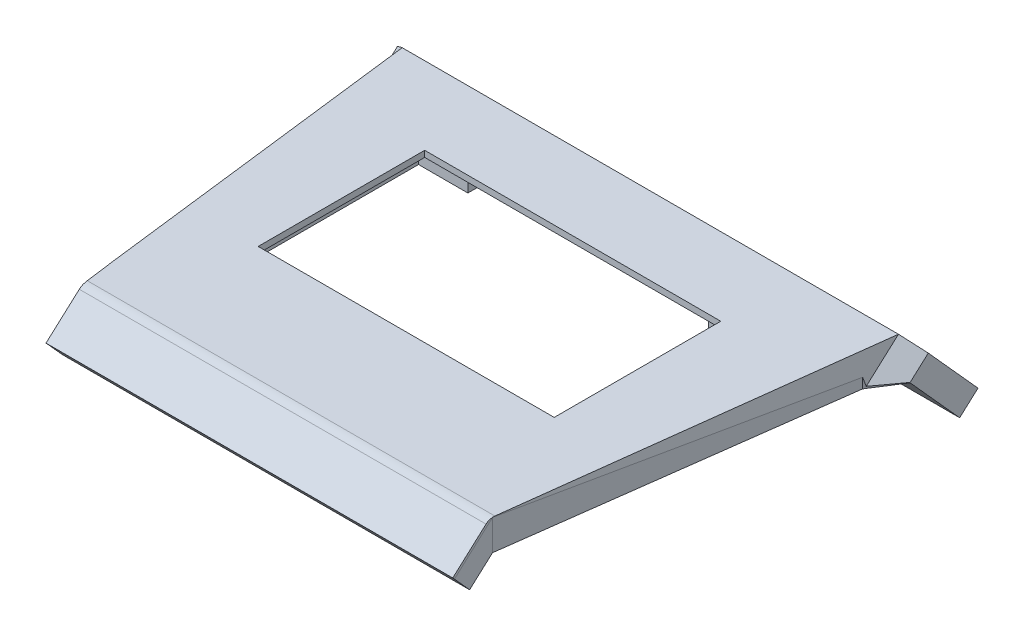
SolidWorks part; units mm, degrees
ref_plane "Front Plane" through (0, 0, 0) normal (0, 0, 1) x (1, 0, 0)
ref_plane "Top Plane" through (0, 0, 0) normal (0, 1, 0) x (1, 0, 0)
ref_plane "Right Plane" through (0, 0, 0) normal (1, 0, 0) x (0, 0, -1)
sketch "Sketch1" plane through (0, 0, 0) normal (0, 1, 0) x (1, 0, 0)
  line L0 (-16.5, -14.5) -> (16.5, -14.5)
  line L1 (16.5, -14.5) -> (20, 12)
  line L2 (-20, 12) -> (-21.25, 14.35)
  line L3 (-21.25, 14.35) -> (21.5, 14.35)
  line L4 (21.5, 14.35) -> (20, 12)
  line L5 (-20, 12) -> (-16.5, -14.5)
  line L7 (-13.75, 9.75) -> (13.75, 9.75)
  line L8 (-13.75, 9.75) -> (-13.75, -9.75)
  line L9 (-13.75, -9.75) -> (13.75, -9.75)
  line L10 (13.75, 9.75) -> (13.75, -9.75)
  dimension "D1" = 27.5
  dimension "D2" = 19.5
  dimension "D3" = 4.75
  dimension "D4" = 9.75
  dimension "D5" = 13.75
  dimension "D6" = 2.75
  dimension "D7" = 2.75
  dimension "D8" = 26.5
  dimension "D9" = 3.5
  dimension "D10" = 3.5
  dimension "D11" = 2.35
  dimension "D12" = 1.25
  dimension "D13" = 1.5
extrude "Boss-Extrude1" add sketch "Sketch1" along normal blind 2.5
sketch "Sketch2" plane through (0, 0, 0) normal (1, 0, 0) x (0, 0, -1)
  line L0 (-14.5, 0) -> (-16.3579, -1.6728)
  line L1 (-16.3579, -1.6728) -> (-17.6961, -0.1865)
  line L2 (-17.6961, -0.1865) -> (-14.7124, 2.5)
  line L3 (-14.5, 2.5) -> (-14.5, 0)
  line L4 (-14.7124, 2.5) -> (-14.5, 2.5)
  line L5 (-1013.75, 0) -> (48986.25, 0) construction
  dimension "D1" = 42
  dimension "D2" = 2
  dimension "D3" = 2.5
extrude "Boss-Extrude2" add sketch "Sketch2" along normal up to vertex (16.5 mm away) and the other way up to vertex (16.5 mm away) up to point (16.5, 2.5, 14.5) other way up to point (-16.5, 2.5, 14.5)
sketch "Sketch3" plane through (0, 0, 0) normal (1, 0, 0) x (0, 0, -1)
  line L0 (-985.65, 0) -> (49014.35, 0) construction
  line L1 (14.35, 2.5) -> (14.7903, 2.5)
  line L2 (14.7903, 2.5) -> (19.8511, -3.1206)
  line L3 (19.8511, -3.1206) -> (18.3648, -4.4589)
  line L4 (18.3648, -4.4589) -> (14.35, 0)
  line L5 (14.35, 0) -> (14.35, 2.5)
  dimension "D1" = 2
  dimension "D2" = 48
  dimension "D3" = 6
extrude "Boss-Extrude3" add sketch "Sketch3" along normal up to vertex (21.5 mm away) and the other way up to vertex (21.25 mm away) up to point (21.5, 2.5, -14.35) other way up to point (-21.25, 2.5, -14.35)
sketch "Sketch4" plane through (0, 8.474, -9.4113) normal (0, 0.6691, -0.7431) x (-1, 0, 0)
  line L0 (-20.1137, -8.0388) -> (-16.4587, 11.7694)
  line L1 (-16.4587, 11.7694) -> (-23.725, 11.7694)
  line L2 (-20.1137, -8.0388) -> (-23.725, -12.0495)
  line L3 (-18.25, 2.6943) -> (-9700.6228, -49050.8648) construction
  line L4 (-16.5, 11.5603) -> (-20, -6.1717) construction
  line L5 (-21.5, -8.0388) -> (21.25, -8.0388) construction
  line L6 (-23.725, -12.0495) -> (-23.725, 11.7694)
  line L7 (19.7575, -4.943) -> (-9662.6153, 49048.6161) construction
  line L9 (20, -6.1717) -> (16.5, 11.5603) construction
  line L10 (20.1137, -8.0388) -> (24.7086, -12.6336)
  line L11 (24.7086, -12.6336) -> (20.8523, 11.7694)
  line L12 (20.8523, 11.7694) -> (16.5, 11.7024)
  line L13 (16.5, 11.7024) -> (20.1137, -8.0388)
  point P11 (-18.25, 2.6943)
  dimension "D1" = 48
  dimension "D2" = 0.25
  dimension "D3" = 0.25
  dimension "D4" = 45
extrude "Cut-Extrude1" cut sketch "Sketch4" against normal through all
sketch "Sketch5" plane through (0, 8.474, -9.4113) normal (0, 0.6691, -0.7431) x (-1, 0, 0)
  line L0 (-21.5, -15.602) -> (21.25, -15.602) construction
  circle A0 centre (-17, -12.352) radius 1.75
  circle A1 centre (17, -12.352) radius 1.75
  dimension "D1" = 3.5
  dimension "D2" = 34
  dimension "D3" = 17
  dimension "D4" = 3.25
extrude "Cut-Extrude2" cut sketch "Sketch5" against normal through all
chamfer "Chamfer1" distance 2 angle 70 1 edges at (0, 0, 9.75) first distance on face at (0, 1.25, 9.75)
sketch "Sketch6" plane through (0, 0, 0) normal (0, -1, 0) x (1, 0, 0)
  line L1 (-13.75, 9.75) -> (-7.75, 9.75)
  line L2 (-13.75, 9.75) -> (-13.75, 14.5)
  line L3 (-13.75, 14.5) -> (-7.75, 14.5)
  line L4 (-7.75, 9.75) -> (-7.75, 14.5)
  line L5 (13.75, 9.75) -> (7.75, 9.75)
  line L6 (13.75, 9.75) -> (13.75, 14.5)
  line L7 (13.75, 14.5) -> (7.75, 14.5)
  line L8 (7.75, 9.75) -> (7.75, 14.5)
  dimension "D1" = 6
  dimension "D2" = 6
extrude "Boss-Extrude4" add sketch "Sketch6" against normal up to surface (2 mm away) up to face at (0, 1.2276, 11.8723)
sketch "Sketch7" plane through (0, 0, 0) normal (0, -1, 0) x (1, 0, 0)
  line L0 (13.75, -9.75) -> (-13.75, -9.75) construction
  line L1 (-9.75, -9.75) -> (9.75, -9.75)
  line L2 (-9.75, -9.75) -> (-9.75, -13.75)
  line L3 (-9.75, -13.75) -> (9.75, -13.75)
  line L4 (9.75, -9.75) -> (9.75, -13.75)
  line L5 (-13.75, -9.75) -> (-13.75, 9.75) construction
  line L6 (13.75, 9.75) -> (13.75, -9.75) construction
  dimension "D1" = 4
  dimension "D2" = 4
  dimension "D3" = 4
extrude "Cut-Extrude3" cut sketch "Sketch7" against normal offset from surface (2 mm away) 0.5 up to face at (-5.5646, 2.5, 4.3551)
sketch "Sketch8" plane through (0, 2.5, 0) normal (0, 1, 0) x (1, 0, 0)
  line L1 (-13.75, 9.75) -> (13.75, 9.75)
  line L2 (-13.75, 9.75) -> (-13.75, -9.75)
  line L3 (-13.75, -9.75) -> (13.75, -9.75)
  line L4 (13.75, 9.75) -> (13.75, -9.75)
  line L5 (-12, 8.5) -> (12, 8.5)
  line L6 (-12, 8.5) -> (-12, -5)
  line L7 (-12, -5) -> (12, -5)
  line L8 (12, 8.5) -> (12, -5)
  dimension "D1" = 4.75
  dimension "D2" = 1.75
  dimension "D3" = 1.75
  dimension "D4" = 1.25
extrude "Boss-Extrude5" add sketch "Sketch8" against normal up to surface (0.5 mm away) up to face at (0, 2, -11.75)
fillet "Fillet1" radius 1 1 edges at (-0.0145, 2.5, 14.7124)
